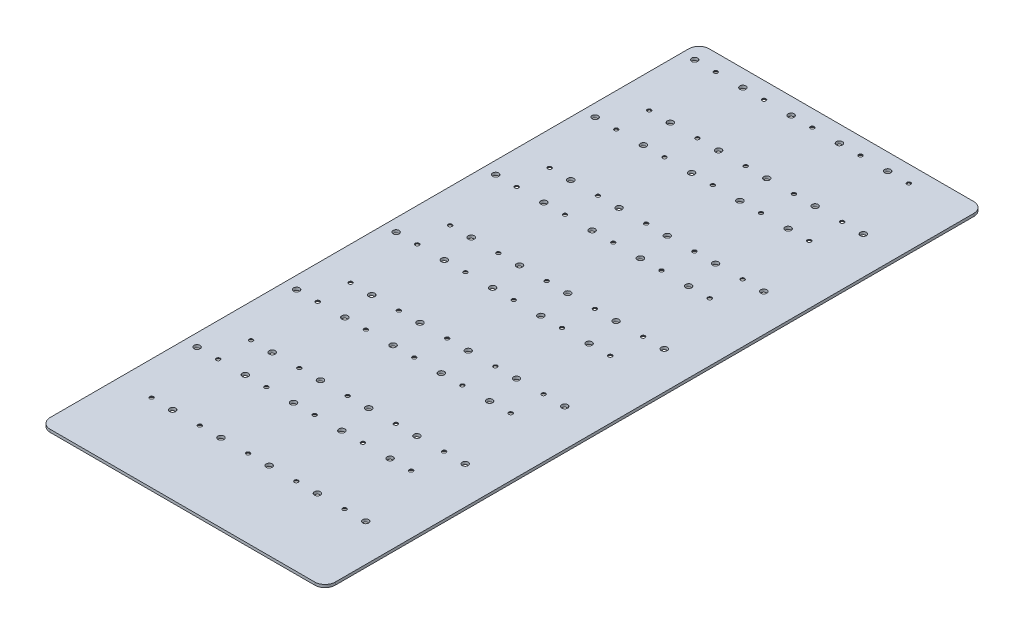
SolidWorks part; units mm, degrees
material "6061 Alloy"
ref_plane "Front Plane" through (0, 0, 0) normal (0, 0, 1) x (1, 0, 0)
ref_plane "Top Plane" through (0, 0, 0) normal (0, 1, 0) x (1, 0, 0)
ref_plane "Right Plane" through (0, 0, 0) normal (1, 0, 0) x (0, 0, -1)
sketch "Sketch1" plane through (0, 0, 0) normal (0, 1, 0) x (1, 0, 0)
  line L0 (0, 289.1112) -> (0, -190.8961) construction
  line L1 (-155.8829, 0) -> (238.1281, 0) construction
  line L8 (118.15, 273.15) -> (-118.15, 273.15)
  line L9 (-118.15, 273.15) -> (-118.15, -273.15)
  line L10 (-118.15, -273.15) -> (118.15, -273.15)
  line L11 (118.15, -273.15) -> (118.15, 273.15)
  point P3 (0, 0)
  point P6 (0, 0)
  point P7 (0, 0)
  point P8 (0, 0)
  point P15 (0, 0)
  dimension "D1" = 546.3
  dimension "D2" = 236.3
extrude "Boss-Extrude1" add sketch "Sketch1" along normal blind 2.286
sketch "Sketch2" plane through (0, 2.286, 0) normal (0, 1, 0) x (1, 0, 0)
  circle A0 centre (-107.8251, 259.25) radius 2.5
  circle A1 centre (-90.3251, 259.25) radius 1.6
  circle A2 centre (-72.8251, 204.05) radius 2.5
  circle A3 centre (-90.3251, 204.05) radius 1.6
  dimension "D1" = 3.2
  dimension "D2" = 3.2
  dimension "D3" = 5
  dimension "D4" = 5
extrude "Cut-Extrude1" cut sketch "Sketch2" against normal through all both
chamfer "Chamfer1" distance 1.8 2 edges at (-90.3251, 0, -257.65) (-90.3251, 0, -202.45)
pattern_linear "LPattern3" count 6 spacing 82.5 along (0, 0, 1) count 5 spacing 40 along (1, 0, 0) of "Chamfer1", "Cut-Extrude1"
fillet "Fillet1" radius 8.5 4 edges at (118.15, 1.143, -273.15) (-118.15, 1.143, 273.15) (118.15, 1.143, 273.15) (-118.15, 1.143, -273.15)
